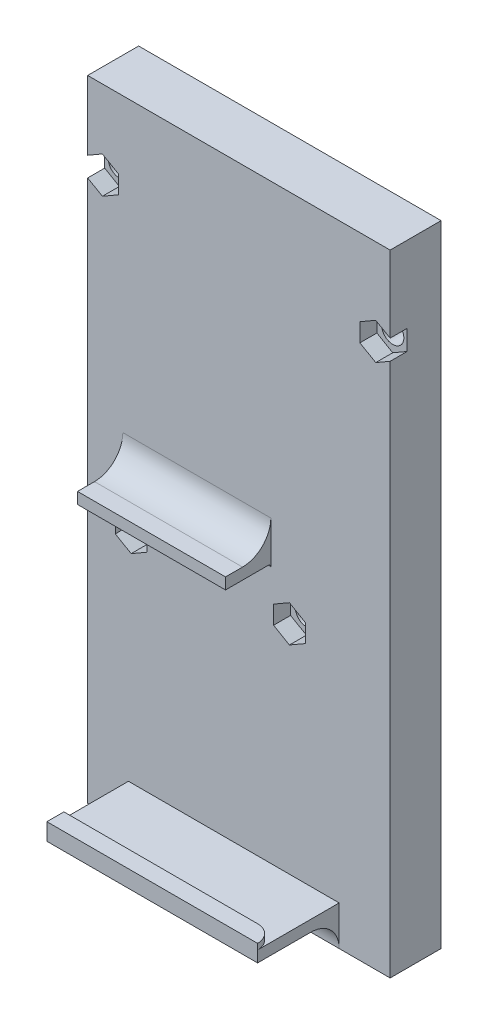
SolidWorks part; units mm, degrees
ref_plane "Front Plane" through (0, 0, 0) normal (0, 0, 1) x (1, 0, 0)
ref_plane "Top Plane" through (0, 0, 0) normal (0, 1, 0) x (1, 0, 0)
ref_plane "Right Plane" through (0, 0, 0) normal (1, 0, 0) x (0, 0, -1)
sketch "Sketch2" plane through (0, 0, 0) normal (0, 0, 1) x (1, 0, 0)
  line L1 (-26.7, 52.15) -> (26.7, 52.15)
  line L2 (-26.7, 52.15) -> (-26.7, -52.15)
  line L3 (-26.7, -52.15) -> (26.7, -52.15)
  line L4 (26.7, 52.15) -> (26.7, -52.15)
  line L5 (-26.7, 52.15) -> (26.7, -52.15) construction
  line L6 (-26.7, -52.15) -> (26.7, 52.15) construction
  point P0 (0, 0)
  dimension "D1" = 104.3
  dimension "D2" = 53.4
extrude "Boss-Extrude1" add sketch "Sketch2" along normal blind 9
sketch "Sketch3" plane through (0, 0, 0) normal (0, 0, -1) x (-1, 0, 0)
  line L1 (26.7, 52.15) -> (26.7, -52.15) construction
  line L2 (-26.7, 52.15) -> (26.7, 52.15) construction
  line L3 (-26.7, -52.15) -> (-26.7, 52.15) construction
  circle A0 centre (24.1, 38.21) radius 1.96
  circle A1 centre (-24.16, 36.91) radius 1.96
  circle A2 centre (-8.92, -13.89) radius 1.96
  circle A3 centre (19.02, -13.89) radius 1.96
  dimension "D3" = 3.92
  dimension "D4" = 2.54
  dimension "D1" = 2.6
  dimension "D2" = 13.94
  dimension "D5" = 15.24
  dimension "D6" = 17.78
  dimension "D7" = 66.04
  dimension "D8" = 7.68
extrude "Cut-Extrude1" cut sketch "Sketch3" against normal through all
sketch "Sketch4" plane through (0, 0, 9) normal (0, 0, 1) x (1, 0, 0)
  line L1 (-20.494, -4.35) -> (5.64, -4.35)
  line L2 (-20.494, -4.35) -> (-20.494, -6.35)
  line L3 (-20.494, -6.35) -> (5.64, -6.35)
  line L4 (5.64, -4.35) -> (5.64, -6.35)
  line L6 (-26.7, -52.15) -> (26.7, -52.15) construction
  line L7 (-26.7, 52.15) -> (-26.7, -52.15) construction
  line L8 (26.7, -52.15) -> (26.7, 52.15) construction
  dimension "D1" = 45.8
  dimension "D2" = 2
  dimension "D3" = 6.206
  dimension "D4" = 21.06
extrude "Boss-Extrude2" add sketch "Sketch4" along normal blind 8
fillet "Fillet1" radius 0.5 1 edges at (-7.427, -6.35, 9)
sketch "Sketch6" plane through (0, 0, 9) normal (0, 0, 1) x (1, 0, 0)
  line L1 (-21.3, 36.5934) -> (-21.3, 39.8266)
  line L2 (-21.3, 39.8266) -> (-24.1, 41.4432)
  line L3 (-24.1, 41.4432) -> (-26.9, 39.8266)
  line L4 (-26.9, 39.8266) -> (-26.9, 36.5934)
  line L5 (-26.9, 36.5934) -> (-24.1, 34.9768)
  line L6 (-24.1, 34.9768) -> (-21.3, 36.5934)
  line L7 (26.96, 35.2934) -> (26.96, 38.5266)
  line L8 (26.96, 38.5266) -> (24.16, 40.1432)
  line L9 (24.16, 40.1432) -> (21.36, 38.5266)
  line L10 (21.36, 38.5266) -> (21.36, 35.2934)
  line L11 (21.36, 35.2934) -> (24.16, 33.6768)
  line L12 (24.16, 33.6768) -> (26.96, 35.2934)
  line L13 (-16.22, -15.5066) -> (-16.22, -12.2734)
  line L14 (-16.22, -12.2734) -> (-19.02, -10.6568)
  line L15 (-19.02, -10.6568) -> (-21.82, -12.2734)
  line L16 (-21.82, -12.2734) -> (-21.82, -15.5066)
  line L17 (-21.82, -15.5066) -> (-19.02, -17.1232)
  line L18 (-19.02, -17.1232) -> (-16.22, -15.5066)
  line L19 (11.72, -15.5066) -> (11.72, -12.2734)
  line L20 (11.72, -12.2734) -> (8.92, -10.6568)
  line L21 (8.92, -10.6568) -> (6.12, -12.2734)
  line L22 (6.12, -12.2734) -> (6.12, -15.5066)
  line L23 (6.12, -15.5066) -> (8.92, -17.1232)
  line L24 (8.92, -17.1232) -> (11.72, -15.5066)
  circle A4 centre (-24.1, 38.21) radius 2.8 construction
  circle A5 centre (24.16, 36.91) radius 2.8 construction
  circle A6 centre (-19.02, -13.89) radius 2.8 construction
  circle A7 centre (8.92, -13.89) radius 2.8 construction
  dimension "D1" = 5.6
  dimension "D2" = 5.6
  dimension "D3" = 5.6
  dimension "D4" = 5.6
extrude "Cut-Extrude3" cut sketch "Sketch6" against normal blind 3
sketch "Sketch8" plane through (0, -52.15, 0) normal (0, -1, 0) x (1, 0, 0)
  line L1 (-26.7, 0) -> (26.7, 0)
  line L2 (-26.7, 0) -> (-26.7, 9)
  line L3 (-26.7, 9) -> (26.7, 9)
  line L4 (26.7, 0) -> (26.7, 9)
extrude "Boss-Extrude4" add sketch "Sketch8" along normal blind 2
sketch "Sketch9" plane through (0, 0, 9) normal (0, 0, 1) x (1, 0, 0)
  line L1 (-19.5, -52.17) -> (17.7, -52.17)
  line L2 (-19.5, -52.17) -> (-19.5, -54.15)
  line L3 (-19.5, -54.15) -> (17.7, -54.15)
  line L4 (17.7, -52.17) -> (17.7, -54.15)
  line L5 (26.7, -54.15) -> (26.7, 35.1433) construction
  line L6 (26.7, -54.15) -> (-26.7, -54.15) construction
  line L8 (-26.7, 36.4779) -> (-26.7, -54.15) construction
  dimension "D1" = 1.98
  dimension "D2" = 9
  dimension "D3" = 7.2
extrude "Boss-Extrude5" add sketch "Sketch9" along normal blind 14.4
sketch "Sketch10" plane through (0, -54.15, 0) normal (0, -1, 0) x (1, 0, 0)
  line L0 (-19.5, 23.4) -> (17.7, 23.4) construction
  line L3 (14.7, 20.4) -> (-19.5, 20.4)
  line L6 (-19.5, 20.4) -> (-19.5, 23.4)
  line L7 (-19.5, 23.4) -> (-19.5, 9) construction
  line L8 (-19.5, 23.4) -> (17.7, 23.4)
  arc A0 (17.7, 23.4) -> (14.7, 20.4) centre (14.7, 23.4) cw
  point P0 (17.7, 23.4)
  dimension "D1" = 3
  dimension "D2" = 3
extrude "Boss-Extrude6" add sketch "Sketch10" against normal blind 3
sketch "Sketch12" plane through (0, -6.35, 0) normal (0, -1, 0) x (-1, 0, 0)
  line L0 (-5.64, -17) -> (-5.64, -9.5) construction
  line L1 (20.494, -17) -> (-5.64, -17) construction
  line L2 (-3.68, -15.04) -> (-3.68, -17) construction
  line L4 (-5.64, -15.04) -> (-3.68, -15.04) construction
  line L6 (20.494, -15.04) -> (20.494, -17)
  line L7 (20.494, -17) -> (-3.68, -17)
  line L8 (-3.68, -15.04) -> (20.494, -15.04)
  line L9 (-3.68, -17) -> (-5.64, -17)
  arc A1 (-5.64, -17) -> (-3.68, -15.04) centre (-3.68, -17) cw
  dimension "D1" = 1.96
fillet "Fillet2" radius 5 1 edges at (-7.427, -4.35, 9)
sketch "Sketch13" plane through (0, -54.15, 0) normal (0, -1, 0) x (1, 0, 0)
  line L1 (-26.7, 9) -> (26.7, 9)
  line L2 (-26.7, 9) -> (-26.7, 0)
  line L3 (-26.7, 0) -> (26.7, 0)
  line L4 (26.7, 9) -> (26.7, 0)
extrude "Boss-Extrude8" add sketch "Sketch13" along normal blind 5
fillet "Fillet3" radius 5 1 edges at (-0.9, -54.15, 9)
